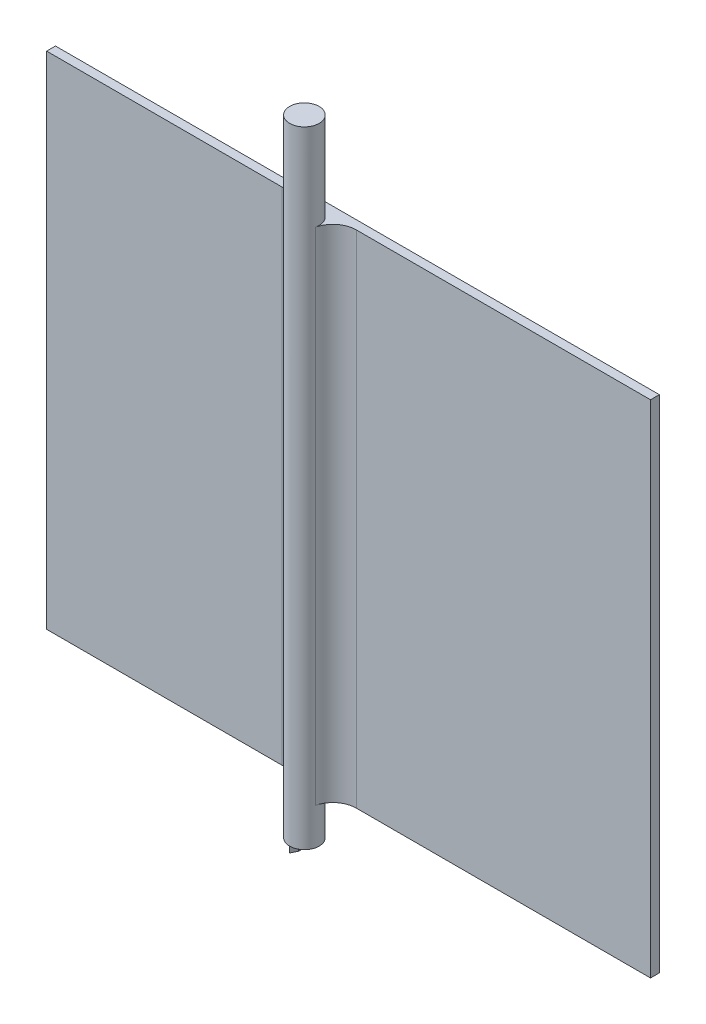
SolidWorks part; units mm, degrees
ref_plane "前视基准面" through (0, 0, 0) normal (0, 0, 1) x (1, 0, 0)
ref_plane "上视基准面" through (0, 0, 0) normal (0, 1, 0) x (1, 0, 0)
ref_plane "右视基准面" through (0, 0, 0) normal (1, 0, 0) x (0, 0, -1)
sketch "草图1" plane through (0, 0, 0) normal (0, 0, 1) x (1, 0, 0)
  line L1 (0, 0) -> (185, 0)
  line L2 (0, 0) -> (0, 170)
  line L3 (0, 170) -> (185, 170)
  line L4 (185, 0) -> (185, 170)
  dimension "D1" = 170
  dimension "D2" = 185
extrude "凸台-拉伸1" add sketch "草图1" along normal blind 3
sketch "草图2" plane through (0, 170, 0) normal (0, 1, 0) x (1, 0, 0)
  line L0 (185, -3) -> (0, -3) construction
  line L1 (87.5, -8) -> (87.5, -3)
  line L2 (97.5, -8) -> (97.5, -3)
  line L3 (87.5, -3) -> (97.5, -3)
  arc A0 (87.5, -8) -> (97.5, -8) centre (92.5, -8) ccw
  dimension "D1" = 10
  dimension "D2" = 5
extrude "凸台-拉伸2" add sketch "草图2" against normal up to surface (170 mm away) up to face at (92.5, 0, 1.5)
sketch "草图3" plane through (0, 170, 0) normal (0, 1, 0) x (1, 0, 0)
  circle A0 centre (92.5, -8) radius 5
extrude "凸台-拉伸3" add sketch "草图3" along normal blind 30
sketch "草图4" plane through (0, 0, 0) normal (0, -1, 0) x (1, 0, 0)
  circle A0 centre (92.5, 8) radius 5
  dimension "D1" = 10
extrude "凸台-拉伸4" add sketch "草图4" along normal blind 12.5
sketch "草图5" plane through (0, 200, 0) normal (0, 1, 0) x (1, 0, 0)
  line L1 (91.5, -11) -> (91.5, -5)
  line L2 (93.5, -11) -> (93.5, -5)
  line L6 (91.5, -5) -> (92.5, -3)
  line L7 (92.5, -3) -> (93.5, -5)
  line L8 (91.5, -11) -> (92.5, -13)
  line L9 (92.5, -13) -> (93.5, -11)
  circle A0 centre (92.5, -8) radius 5 construction
  arc A1 (97.5, -8) -> (87.5, -8) centre (92.5, -8) ccw construction
  point P1 (92.5, -8)
  dimension "D1" = 1
  dimension "D2" = 6
sketch "草图6" plane through (0, -12.5, 0) normal (0, -1, 0) x (1, 0, 0)
  line L0 (92.5, 13) -> (93.5, 11) construction
  line L1 (91.5, 11) -> (92.5, 13) construction
  line L2 (91.5, 5) -> (92.5, 3) construction
  line L3 (92.5, 3) -> (93.5, 5) construction
  line L4 (93.5, 11) -> (93.5, 5) construction
  line L5 (91.5, 11) -> (91.5, 5) construction
  line L6 (92.5, 13) -> (93.5, 11)
  line L7 (91.5, 11) -> (92.5, 13)
  line L8 (91.5, 5) -> (92.5, 3)
  line L9 (92.5, 3) -> (93.5, 5)
  line L10 (93.5, 11) -> (93.5, 5)
  line L11 (91.5, 11) -> (91.5, 5)
  circle A1 centre (92.5, 8) radius 5
  circle A2 centre (92.5, 8) radius 5
  dimension "D1" = 0
extrude "凸台-拉伸5" add sketch "草图6" along normal blind 2 contours L7 L11 L8 L9 L10 L6 region at (92.5, -12.5, 8)
fillet "圆角1" radius 8 2 edges at (97.5, 85, 3) (87.5, 85, 3)
sketch "草图7" plane through (0, 0, 0) normal (0, -1, 0) x (1, 0, 0)
  line L1 (185, 3) -> (205, 3)
  line L2 (185, 3) -> (185, 0)
  line L3 (185, 0) -> (205, 0)
  line L4 (205, 3) -> (205, 0)
  dimension "D1" = 3
  dimension "D2" = 20
extrude "凸台-拉伸6" add sketch "草图7" against normal up to surface (170 mm away) up to face at (92.5, 170, 2.6811)
